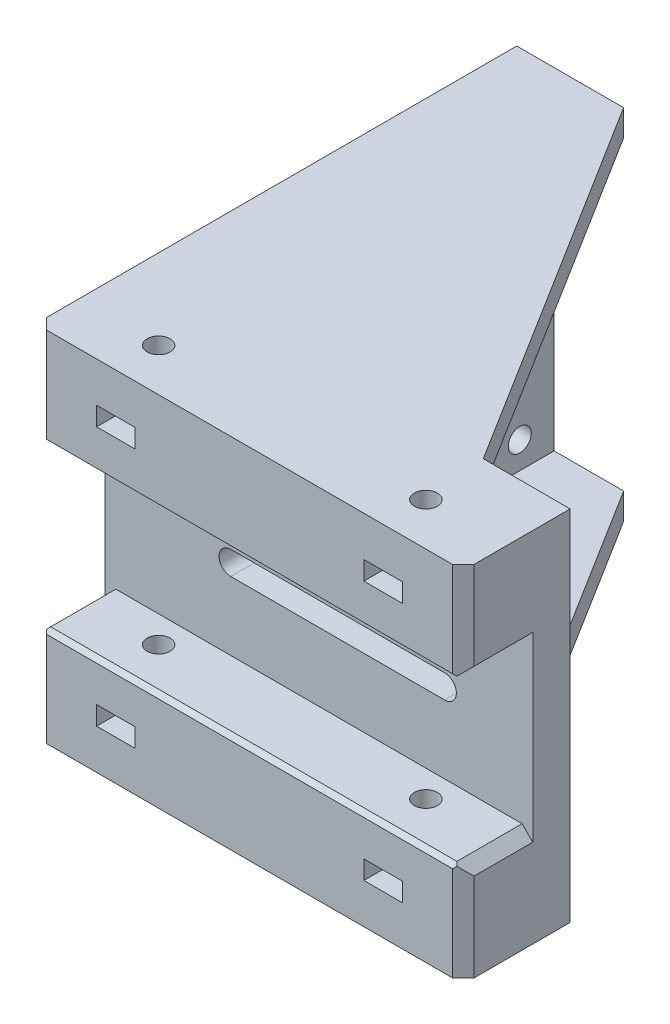
SolidWorks part; units mm, degrees
ref_plane "Front Plane" through (0, 0, 0) normal (0, 0, 1) x (1, 0, 0)
ref_plane "Top Plane" through (0, 0, 0) normal (0, 1, 0) x (1, 0, 0)
ref_plane "Right Plane" through (0, 0, 0) normal (1, 0, 0) x (0, 0, -1)
sketch "Sketch1" plane through (0, 0, 0) normal (0, 1, 0) x (1, 0, 0)
  line L0 (0, 0) -> (0, 90)
  line L1 (0, 90) -> (7, 90)
  line L2 (7, 90) -> (7, 20)
  line L3 (7, 20) -> (70, 20)
  line L4 (70, 20) -> (70, 0)
  line L5 (70, 0) -> (0, 0)
  dimension "D1" = 90
  dimension "D2" = 20
  dimension "D3" = 7
  dimension "D4" = 70
extrude "Boss-Extrude1" add sketch "Sketch1" along normal blind 67
sketch "Sketch2" plane through (7, 0, 0) normal (1, 0, 0) x (0, 0, -1)
  line L0 (90, 33.5) -> (60, 33.5) construction
  line L1 (90, 67) -> (90, 0) construction
  line L3 (36.43, 9.93) -> (83.57, 9.93) construction
  line L4 (36.43, 9.93) -> (36.43, 57.07) construction
  line L5 (36.43, 57.07) -> (83.57, 57.07) construction
  line L6 (83.57, 9.93) -> (83.57, 57.07) construction
  line L7 (36.43, 9.93) -> (83.57, 57.07) construction
  line L8 (36.43, 57.07) -> (83.57, 9.93) construction
  circle A0 centre (83.57, 57.07) radius 2.15
  circle A1 centre (36.43, 57.07) radius 2.15
  circle A2 centre (36.43, 9.93) radius 2.15
  circle A3 centre (83.57, 9.93) radius 2.15
  circle A4 centre (60, 33.5) radius 19.1
  dimension "D4" = 2
  dimension "D1" = 47.14
  dimension "D2" = 47.14
  dimension "D3" = 30
  dimension "D5" = 2
extrude "Cut-Extrude1" cut sketch "Sketch2" against normal blind 67
sketch "Sketch3" plane through (7, 0, 0) normal (1, 0, 0) x (0, 0, -1)
  line L0 (90, 67) -> (90, 0) construction
  line L1 (20, 67) -> (90, 67)
  line L2 (20, 67) -> (20, 62.1)
  line L3 (20, 62.1) -> (90, 62.1)
  line L4 (90, 67) -> (90, 62.1)
  line L6 (20, 0) -> (90, 0)
  line L7 (20, 0) -> (20, 4.9)
  line L8 (20, 4.9) -> (90, 4.9)
  line L9 (90, 0) -> (90, 4.9)
  dimension "D1" = 4.9
  dimension "D2" = 4.9
extrude "Boss-Extrude2" add sketch "Sketch3" along normal up to surface (63 mm away) up to face at (70, 33.5, -10)
sketch "Sketch4" plane through (70, 0, 0) normal (1, 0, 0) x (0, 0, -1)
  line L0 (0, 0) -> (90, 0) construction
  line L1 (0, 67) -> (20, 67)
  line L2 (0, 67) -> (0, 0)
  line L3 (0, 0) -> (20, 0)
  line L4 (20, 67) -> (20, 0)
  dimension "D1" = 20
extrude "Boss-Extrude3" add sketch "Sketch4" along normal blind 10
chamfer "Chamfer1" distance 80 distance2 50 2 edges at (70, 2.45, -90) (70, 64.55, -90) first distance on face at (70, 2.45, -55) first distance on face at (70, 64.55, -55)
sketch "Sketch6" plane through (0, 0, 0) normal (0, 0, 1) x (1, 0, 0)
  line L0 (0, 33.5) -> (80, 33.5) construction
  line L1 (0, 67) -> (0, 0) construction
  line L2 (80, 67) -> (80, 0) construction
  line L4 (0, 18.5) -> (80, 18.5)
  line L5 (0, 18.5) -> (0, 48.5)
  line L6 (0, 48.5) -> (80, 48.5)
  line L7 (80, 18.5) -> (80, 48.5)
  line L8 (0, 18.5) -> (80, 48.5) construction
  line L9 (0, 48.5) -> (80, 18.5) construction
  point P6 (40, 33.5)
  dimension "D1" = 30
extrude "Cut-Extrude2" cut sketch "Sketch6" against normal blind 13
sketch "Sketch7" plane through (0, 67, 0) normal (0, 1, 0) x (1, 0, 0)
  line L0 (0, 0) -> (0, 8) construction
  line L1 (0, 8) -> (15, 8) construction
  line L2 (15, 8) -> (65, 8) construction
  circle A0 centre (15, 8) radius 2.15
  circle A1 centre (65, 8) radius 2.15
  dimension "D1" = 4.3
  dimension "D2" = 4.3
  dimension "D3" = 15
  dimension "D4" = 50
extrude "Cut-Extrude3" cut sketch "Sketch7" against normal blind 100
sketch "Sketch8" plane through (0, 0, -20) normal (0, 0, -1) x (-1, 0, 0)
  line L0 (-80, 33.5) -> (-7, 33.5) construction
  line L1 (-80, 0) -> (-80, 67) construction
  line L2 (-7, 62.1) -> (-7, 4.9) construction
  line L3 (-63.5, 33.5) -> (-23.5, 33.5) construction
  line L5 (-63.5, 35.7) -> (-23.5, 35.7)
  line L6 (-63.5, 31.3) -> (-23.5, 31.3)
  arc A0 (-63.5, 35.7) -> (-63.5, 31.3) centre (-63.5, 33.5) ccw
  arc A1 (-23.5, 31.3) -> (-23.5, 35.7) centre (-23.5, 33.5) ccw
  point P10 (-43.5, 33.5)
  dimension "D1" = 2.2
extrude "Cut-Extrude4" cut sketch "Sketch8" against normal blind 100
fillet "Fillet2" radius 8 1 edges at (7, 33.5, -20)
sketch "Sketch9" plane through (0, 0, 0) normal (0, 0, 1) x (1, 0, 0)
  line L0 (0, 57.75) -> (15, 57.75) construction
  line L1 (0, 67) -> (0, 48.5) construction
  line L2 (15, 57.75) -> (65, 57.75) construction
  line L3 (0, 33.5) -> (80, 33.5) construction
  line L4 (0, 48.5) -> (0, 18.5) construction
  line L5 (80, 18.5) -> (80, 48.5) construction
  line L6 (61.4, 56) -> (61.4, 59.5)
  line L7 (11.4, 56) -> (18.6, 56)
  line L8 (11.4, 56) -> (11.4, 59.5)
  line L9 (11.4, 59.5) -> (18.6, 59.5)
  line L10 (18.6, 56) -> (18.6, 59.5)
  line L11 (11.4, 56) -> (18.6, 59.5) construction
  line L12 (11.4, 59.5) -> (18.6, 56) construction
  line L13 (61.4, 56) -> (68.6, 56)
  line L14 (68.6, 56) -> (68.6, 59.5)
  line L15 (61.4, 59.5) -> (68.6, 59.5)
  line L16 (61.4, 7.5) -> (61.4, 11)
  line L17 (61.4, 7.5) -> (68.6, 7.5)
  line L18 (68.6, 7.5) -> (68.6, 11)
  line L19 (61.4, 11) -> (68.6, 11)
  line L20 (11.4, 7.5) -> (11.4, 11)
  line L21 (11.4, 7.5) -> (18.6, 7.5)
  line L22 (18.6, 7.5) -> (18.6, 11)
  line L23 (11.4, 11) -> (18.6, 11)
  dimension "D1" = 15
  dimension "D2" = 50
  dimension "D3" = 3.5
  dimension "D4" = 7.2
  dimension "D5" = 2
  dimension "D6" = 2
extrude "Cut-Extrude5" cut sketch "Sketch9" against normal blind 14
chamfer "Chamfer2" distance 2 angle 45 4 edges at (80, 18.5, -6.5) (80, 48.5, -6.5) (0, 48.5, -6.5) (0, 18.5, -6.5)
chamfer "Chamfer3" distance 2 angle 45 4 edges at (80, 58.75, 0) (80, 8.25, 0) (0, 58.75, 0) (0, 8.25, 0)
chamfer "Chamfer4" distance 0.8 angle 45 2 edges at (40, 18.5, 0) (40, 48.5, 0)
chamfer "Chamfer5" distance 3 angle 45 1 edges at (0, 33.5, -79.1)
